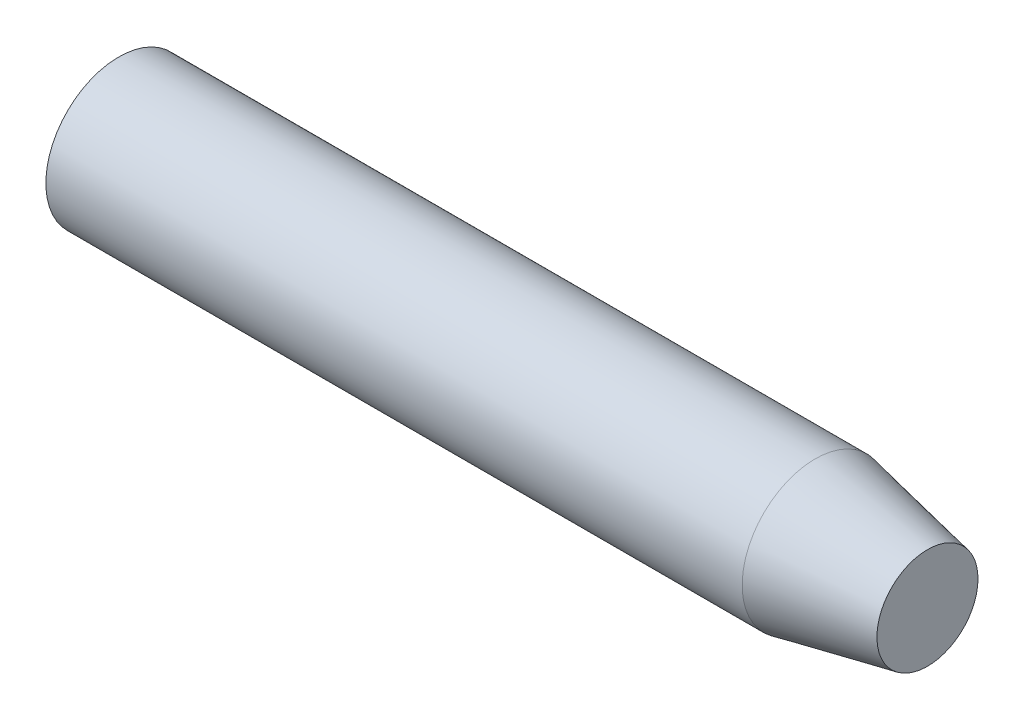
SolidWorks part; units mm, degrees
ref_plane "Front Plane" through (0, 0, 0) normal (0, 0, 1) x (1, 0, 0)
ref_plane "Top Plane" through (0, 0, 0) normal (0, 1, 0) x (1, 0, 0)
ref_plane "Right Plane" through (0, 0, 0) normal (1, 0, 0) x (0, 0, -1)
sketch "Sketch1" plane through (0, 0, 0) normal (0, 0, 1) x (1, 0, 0)
  line L0 (26, 6.5) -> (36, 4.5)
  line L1 (-36, 6.5) -> (26, 6.5)
  line L2 (-36, 6.5) -> (-36, 4)
  line L3 (-36, 4) -> (26, 4)
  line L5 (36, 4.5) -> (36, 0)
  line L6 (36, 0) -> (-36, 0) construction
  line L7 (26, 4) -> (26, 0)
  line L8 (26, 0) -> (36, 0)
  dimension "D1" = 13
  dimension "D2" = 72
  dimension "D3" = 2.5
  dimension "D4" = 10
  dimension "D5" = 9
revolve "Revolve1" add sketch "Sketch1" angle 360 about L6
ref_axis "Axis1" through (-36, 0, 0) along (1, 0, 0)
ref_point "Point1"
ref_point "Point2"
